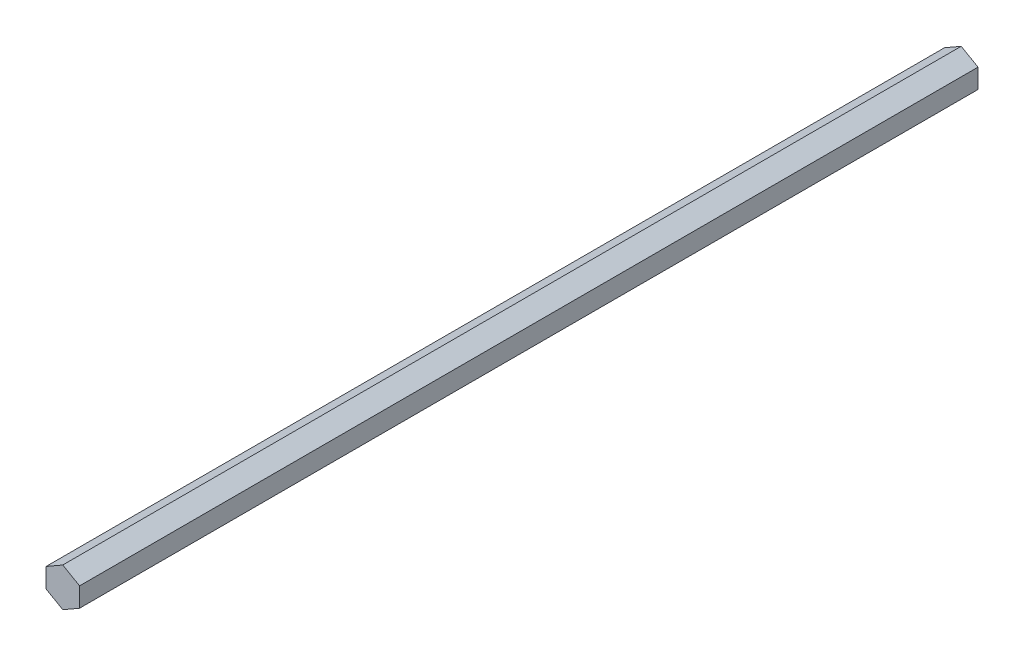
SolidWorks part; units mm, degrees
ref_plane "Front Plane" through (0, 0, 0) normal (0, 0, 1) x (1, 0, 0)
ref_plane "Top Plane" through (0, 0, 0) normal (0, 1, 0) x (1, 0, 0)
ref_plane "Right Plane" through (0, 0, 0) normal (1, 0, 0) x (0, 0, -1)
sketch "Sketch1" plane through (0, 0, 0) normal (0, 0, 1) x (1, 0, 0)
  line L1 (0, 7.3323) -> (-6.35, 3.6662)
  line L2 (-6.35, 3.6662) -> (-6.35, -3.6662)
  line L3 (-6.35, -3.6662) -> (0, -7.3323)
  line L4 (0, -7.3323) -> (6.35, -3.6662)
  line L5 (6.35, -3.6662) -> (6.35, 3.6662)
  line L6 (6.35, 3.6662) -> (0, 7.3323)
  circle A0 centre (0, 0) radius 6.35 construction
  dimension "D1" = 12.7
extrude "Boss-Extrude1" add sketch "Sketch1" along normal blind 340
ref_axis "Axis1" through (0, 0, 0) along (0, 0, 1)
